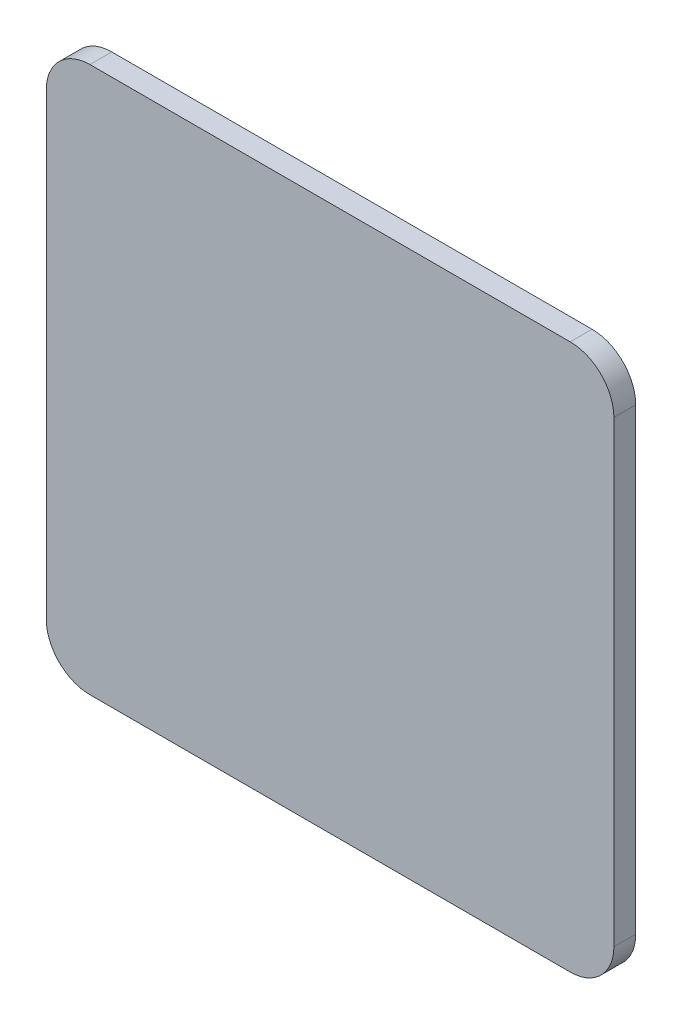
SolidWorks part; units mm, degrees
ref_plane "Front Plane" through (0, 0, 0) normal (0, 0, 1) x (1, 0, 0)
ref_plane "Top Plane" through (0, 0, 0) normal (0, 1, 0) x (1, 0, 0)
ref_plane "Right Plane" through (0, 0, 0) normal (1, 0, 0) x (0, 0, -1)
sketch "Sketch1" plane through (0, 0, 0) normal (0, 0, 1) x (1, 0, 0)
  line L1 (-27.94, -31.75) -> (27.94, -31.75)
  line L2 (-33.02, -26.67) -> (-33.02, 26.67)
  line L3 (-27.94, 31.75) -> (27.94, 31.75)
  line L4 (33.02, -26.67) -> (33.02, 26.67)
  line L5 (-33.02, -31.75) -> (33.02, 31.75) construction
  line L6 (-33.02, 31.75) -> (33.02, -31.75) construction
  arc A0 (-27.94, -31.75) -> (-33.02, -26.67) centre (-27.94, -26.67) cw
  arc A1 (27.94, -31.75) -> (33.02, -26.67) centre (27.94, -26.67) ccw
  arc A2 (27.94, 31.75) -> (33.02, 26.67) centre (27.94, 26.67) cw
  arc A3 (-33.02, 26.67) -> (-27.94, 31.75) centre (-27.94, 26.67) cw
  point P0 (0, 0)
  dimension "D3" = 5.08
  dimension "D1" = 66.04
  dimension "D2" = 63.5
extrude "Boss-Extrude1" add sketch "Sketch1" along normal blind 2.54
